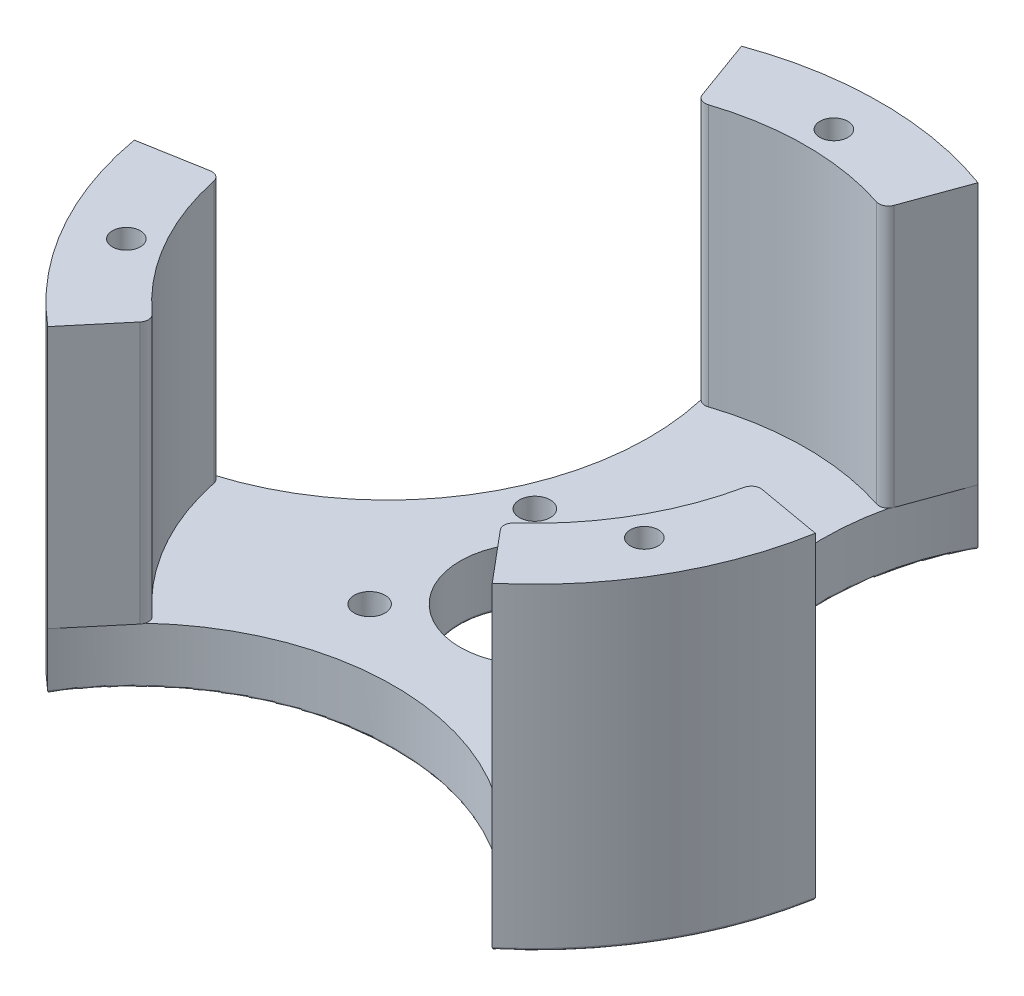
SolidWorks part; units mm, degrees
ref_plane "Front Plane" through (0, 0, 0) normal (0, 0, 1) x (1, 0, 0)
ref_plane "Top Plane" through (0, 0, 0) normal (0, 1, 0) x (1, 0, 0)
ref_plane "Right Plane" through (0, 0, 0) normal (1, 0, 0) x (0, 0, -1)
sketch "Sketch1" plane through (0, 0, 0) normal (0, 1, 0) x (1, 0, 0)
  line L1 (-8.8388, -8.8388) -> (8.8388, -8.8388) construction
  line L2 (-8.8388, -8.8388) -> (-8.8388, 8.8388) construction
  line L3 (-8.8388, 8.8388) -> (8.8388, 8.8388) construction
  line L4 (8.8388, -8.8388) -> (8.8388, 8.8388) construction
  line L5 (-8.8388, -8.8388) -> (8.8388, 8.8388) construction
  line L6 (-8.8388, 8.8388) -> (8.8388, -8.8388) construction
  circle A0 centre (0, 0) radius 37
  circle A1 centre (-8.8388, 8.8388) radius 1.65
  circle A2 centre (8.8388, 8.8388) radius 1.65
  circle A3 centre (8.8388, -8.8388) radius 1.65
  circle A4 centre (-8.8388, -8.8388) radius 1.65
  dimension "D1" = 74
  dimension "D4" = 3.3
  dimension "D2" = 12.5
extrude "Boss-Extrude1" add sketch "Sketch1" along normal blind 6
sketch "Sketch2" plane through (0, 6, 0) normal (0, 1, 0) x (1, 0, 0)
  line L0 (-12.6547, 34.7686) -> (0, 0) construction
  line L1 (0, 0) -> (12.6547, 34.7686) construction
  line L2 (0, -1000) -> (0, 49000) construction
  line L3 (-12.6547, 34.7686) -> (-9.9186, 27.2511)
  line L4 (9.9186, 27.2511) -> (12.6547, 34.7686)
  arc A0 (12.6547, 34.7686) -> (-12.6547, 34.7686) centre (0, 0) ccw
  circle A1 centre (0, 0) radius 37 construction
  arc A2 (9.9186, 27.2511) -> (-9.9186, 27.2511) centre (0, 0) ccw
  circle A3 centre (0, 32) radius 1.5
  dimension "D1" = 8
  dimension "D5" = 3
  dimension "D2" = 20
  dimension "D3" = 20
  dimension "D4" = 32
extrude "Boss-Extrude2" add sketch "Sketch2" along normal blind 28
sketch "Sketch16" plane through (0, 34, 0) normal (0, 1, 0) x (1, 0, 0)
  circle A0 centre (0, 32) radius 1.5
  circle A1 centre (0, 32) radius 1.5 construction
extrude "Cut-Extrude9" cut sketch "Sketch16" against normal through all
pattern_circular "CirPattern1" count 3 over 360 about axis through (0, 6, 0) along (0, -1, 0) of "Boss-Extrude2", "Cut-Extrude9" reverse direction yes
sketch "Sketch3" plane through (0, 6, 0) normal (0, 1, 0) x (1, 0, 0)
  circle A0 centre (0, 0) radius 8
  dimension "D1" = 16
extrude "Cut-Extrude1" cut sketch "Sketch3" against normal blind 10
sketch "Sketch4" plane through (0, 0, 0) normal (0, -1, 0) x (1, 0, 0)
  circle A0 centre (8.8388, 8.8388) radius 3.5
  circle A1 centre (8.8388, -8.8388) radius 3.5
  circle A2 centre (-8.8388, -8.8388) radius 3.5
  circle A3 centre (-8.8388, 8.8388) radius 3.5
  dimension "D1" = 7
extrude "Cut-Extrude2" cut sketch "Sketch4" against normal blind 3
sketch "Sketch5" plane through (0, 6, 0) normal (0, 1, 0) x (1, 0, 0)
  circle A1 centre (37.307, 21.5392) radius 27.9777
extrude "Cut-Extrude3" cut sketch "Sketch5" against normal through all
pattern_circular "CirPattern2" count 3 over 360 about axis through (0, 6, 0) along (0, -1, 0) of "Cut-Extrude3" reverse direction yes
fillet "Fillet1" radius 0.25 16 edges at (0, 0, 15.1007) (32.0429, 0, 18.5) (9.3808, 0, -23.2349) (22.2819, 0, 2.0616) (0, 0, -37) (-22.2819, 0, 2.0616) (-9.3808, 0, -23.2349) (-32.0429, 0, 18.5) (0, 0, 8) (8.8388, 0, 5.3388) (5.6425, 0, -7.4129) (-5.6425, 0, -7.4129) (-8.8388, 0, 5.3388) (0, 0, -30.5) (26.4138, 0, 15.25) (-26.4138, 0, 15.25)
fillet "Fillet2" radius 1 6 edges at (28.5594, 20, 5.0358) (9.9186, 20, -27.2511) (-9.9186, 20, -27.2511) (18.6408, 20, 22.2153) (-28.5594, 20, 5.0358) (-18.6408, 20, 22.2153)
sketch "Sketch6" plane through (0, 34, 0) normal (0, 1, 0) x (1, 0, 0)
  line L0 (0, 32) -> (0, 0) construction
  line L1 (0, 0) -> (-27.7128, -16) construction
  line L2 (0, 0) -> (27.7128, -16) construction
  circle A0 centre (0, 0) radius 6
  circle A1 centre (15.5885, -9) radius 12
  circle A2 centre (0, 18) radius 12
  circle A3 centre (-15.5885, -9) radius 12
  point P7 (15.5885, -9)
  point P9 (0, 18)
  point P10 (-15.5885, -9)
  dimension "D1" = 12
  dimension "D2" = 24
sketch "Sketch7" plane through (0, 34, 0) normal (0, 1, 0) x (1, 0, 0)
  circle A0 centre (0, 0) radius 18
  circle A1 centre (0, 0) radius 13
  dimension "D1" = 26
  dimension "D2" = 5
ref_plane "Plane1" through (0, 29, 0) normal (0, 1, 0) x (1, 0, 0)
